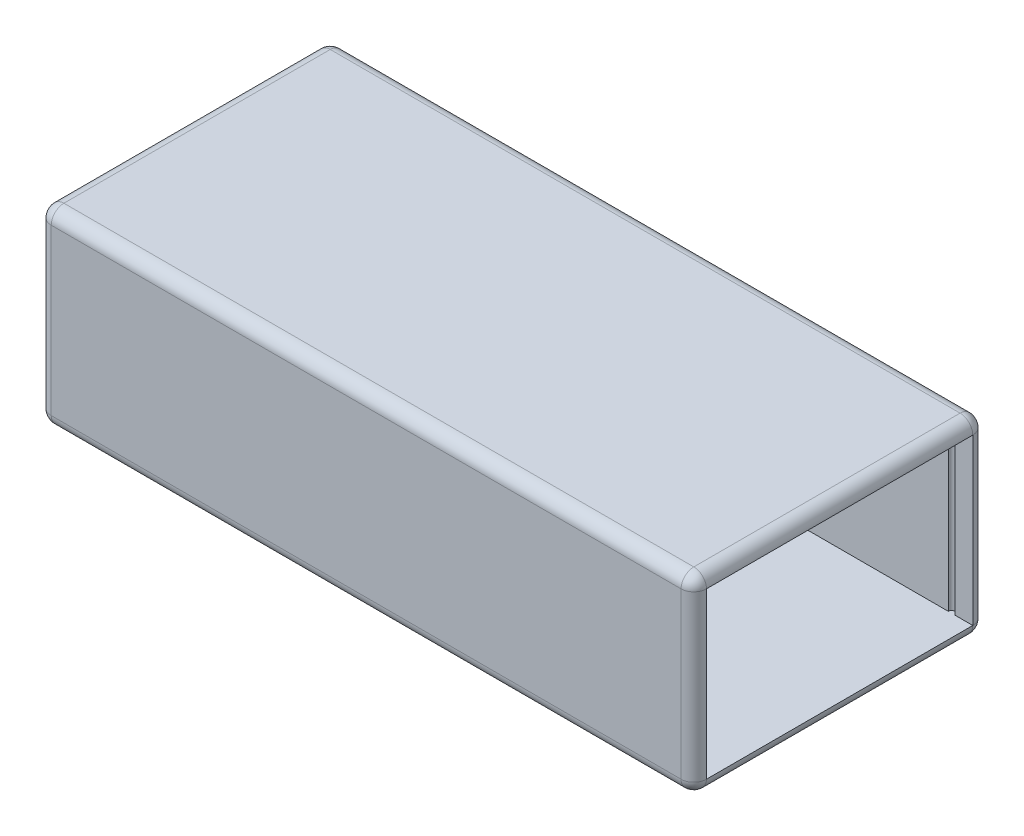
SolidWorks part; units mm, degrees
ref_plane "Plano frontal" through (0, 0, 0) normal (0, 0, 1) x (1, 0, 0)
ref_plane "Plano superior" through (0, 0, 0) normal (0, 1, 0) x (1, 0, 0)
ref_plane "Plano direito" through (0, 0, 0) normal (1, 0, 0) x (0, 0, -1)
sketch "Esboço1" plane through (0, 0, 0) normal (0, 1, 0) x (1, 0, 0)
  line L1 (0, 0) -> (155, 0)
  line L2 (0, 0) -> (0, 69)
  line L3 (0, 69) -> (155, 69)
  line L4 (155, 0) -> (155, 69)
  dimension "D1" = 69
  dimension "D2" = 155
extrude "Ressalto-extrusão1" add sketch "Esboço1" along normal blind 42
sketch "Esboço2" plane through (0, 42, 0) normal (0, 1, 0) x (1, 0, 0)
  line L0 (0, 0) -> (155, 0) construction
  line L1 (2, 3) -> (155, 3)
  line L2 (2, 3) -> (2, 66)
  line L3 (2, 66) -> (155, 66)
  line L4 (155, 3) -> (155, 66)
  line L5 (155, 69) -> (0, 69) construction
  line L6 (0, 69) -> (0, 0) construction
  dimension "D1" = 3
  dimension "D2" = 3
  dimension "D3" = 2
  dimension "D4" = 0
extrude "Corte-extrusão1" cut sketch "Esboço2" against normal offset from surface (39 mm away) 3 up to face at (77.5, 0, -34.5)
sketch "Esboço5" plane through (0, 42, 0) normal (0, 1, 0) x (1, 0, 0)
  line L0 (155, 66) -> (155, 69) construction
  line L1 (2, 3) -> (122.5, 3)
  line L2 (2, 3) -> (2, 5)
  line L3 (2, 5) -> (122.5, 5)
  line L4 (122.5, 3) -> (122.5, 5)
  line L5 (2, 66) -> (122.5, 66)
  line L6 (2, 66) -> (2, 64)
  line L7 (2, 64) -> (122.5, 64)
  line L8 (122.5, 66) -> (122.5, 64)
  point P13 (155, 67.5)
  dimension "D1" = 2
  dimension "D2" = 2
  dimension "D3" = 32.5
  dimension "D4" = 32.5
extrude "Ressalto-extrusão3" add sketch "Esboço5" against normal offset from surface (8.25 mm away) 26.5 from offset 4.25 up to face at (78.5, 3, -34.5) offset against normal yes
sketch "Esboço7" plane through (0, 42, 0) normal (0, 1, 0) x (1, 0, 0)
  line L0 (2, 3) -> (155, 3) construction
  line L1 (155, 66) -> (2, 66) construction
  line L2 (155, 66) -> (155, 69) construction
  circle A0 centre (150, 3) radius 0.8
  circle A1 centre (150, 66) radius 0.8
  dimension "D1" = 5
  dimension "D2" = 5
  dimension "D3" = 1.6
  dimension "D4" = 1.6
extrude "Corte-extrusão4" cut sketch "Esboço7" against normal up to surface (39 mm away) up to face at (78.5, 3, -34.5)
fillet "Filete5" [suppressed] radius 3
sketch "Esboço8" plane through (0, 42, 0) normal (0, 1, 0) x (1, 0, 0)
  line L0 (0, 0) -> (155, 0) construction
  line L1 (155, 0) -> (155, 3) construction
  line L2 (0, 69) -> (0, 0) construction
  line L3 (155, 69) -> (0, 69) construction
  line L4 (155, 66) -> (155, 69) construction
  circle A0 centre (3, 3) radius 0.9
  circle A1 centre (120, 3) radius 0.9
  circle A2 centre (120, 66) radius 0.9
  circle A3 centre (3, 66) radius 0.9
  dimension "D1" = 1.8
  dimension "D2" = 1.8
  dimension "D3" = 1.8
  dimension "D4" = 1.8
  dimension "D5" = 3
  dimension "D6" = 35
  dimension "D7" = 3
  dimension "D8" = 3
  dimension "D9" = 3
  dimension "D10" = 3
  dimension "D11" = 35
  dimension "D12" = 3
extrude "Corte-extrusão3" [suppressed] cut sketch "Esboço8" against normal up to surface (8.5 mm away)
sketch "Esboço10" plane through (0, 42, 0) normal (0, 1, 0) x (1, 0, 0)
  line L0 (2, 3) -> (149.2, 3) construction
  line L1 (149.2, 66) -> (2, 66) construction
  line L2 (2, 66) -> (2, 3) construction
  line L3 (2, 66) -> (2, 3) construction
  circle A0 centre (7, 3) radius 0.75
  circle A1 centre (7, 66) radius 0.75
  dimension "D1" = 1.5
  dimension "D2" = 1.5
  dimension "D3" = 5
  dimension "D4" = 5
extrude "Ressalto-extrusão5" add sketch "Esboço10" against normal up to surface (4.25 mm away) up to face at (62.25, 37.75, -4)
sketch "Esboço9" plane through (0, 42, 0) normal (0, 1, 0) x (1, 0, 0)
  line L0 (2, 66) -> (2, 3) construction
  line L1 (155, 0) -> (0, 0)
  line L2 (155, 0) -> (155, 69)
  line L3 (155, 69) -> (0, 69)
  line L4 (0, 0) -> (0, 69)
  line L5 (149.2, 66) -> (7.75, 66) construction
  dimension "D1" = 69
  dimension "D2" = 155
  dimension "D3" = 2
  dimension "D4" = 3
extrude "Ressalto-extrusão4" add sketch "Esboço9" along normal blind 3
fillet "Filete6" radius 3 8 edges at (0, 21, -69) (0, 0, -34.5) (0, 21, 0) (77.5, 0, 0) (155, 21, 0) (77.5, 0, -69) (155, 0, -34.5) (155, 21, -69)
fillet "Filete7" radius 3 4 edges at (77.5, 45, 0) (0, 45, -34.5) (155, 45, -34.5) (77.5, 45, -69)
sketch "Esboço11" plane through (0, 0, 0) normal (-1, 0, 0) x (0, 0, 1)
  line L1 (-62.35, 37) -> (-44.25, 37)
  line L2 (-62.35, 37) -> (-62.35, 21.9)
  line L3 (-62.35, 21.9) -> (-44.25, 21.9)
  line L4 (-44.25, 37) -> (-44.25, 21.9)
extrude "Ressalto-extrusão6" add sketch "Esboço11" along normal blind 5
sketch "Esboço12" plane through (-5, 0, 0) normal (-1, 0, 0) x (0, 0, 1)
  line L1 (-60.8, 35.25) -> (-45.8, 35.25)
  line L2 (-60.8, 35.25) -> (-60.8, 23.75)
  line L3 (-60.8, 23.75) -> (-45.8, 23.75)
  line L4 (-45.8, 35.25) -> (-45.8, 23.75)
extrude "Corte-extrusão5" cut sketch "Esboço12" against normal blind 9
sketch "Esboço14" plane through (-5, 0, 0) normal (-1, 0, 0) x (0, 0, 1)
  line L0 (-62.35, 21.9) -> (-44.25, 21.9) construction
  line L1 (-60.05, 21.9) -> (-46.55, 21.9)
  line L2 (-60.05, 21.9) -> (-60.05, 23.75)
  line L3 (-60.05, 23.75) -> (-46.55, 23.75)
  line L4 (-46.55, 21.9) -> (-46.55, 23.75)
  line L5 (-60.8, 23.75) -> (-45.8, 23.75) construction
  line L6 (-62.35, 37) -> (-62.35, 21.9) construction
  dimension "D1" = 13.5
  dimension "D2" = 2.3
extrude "Corte-extrusão6" cut sketch "Esboço14" against normal through all
